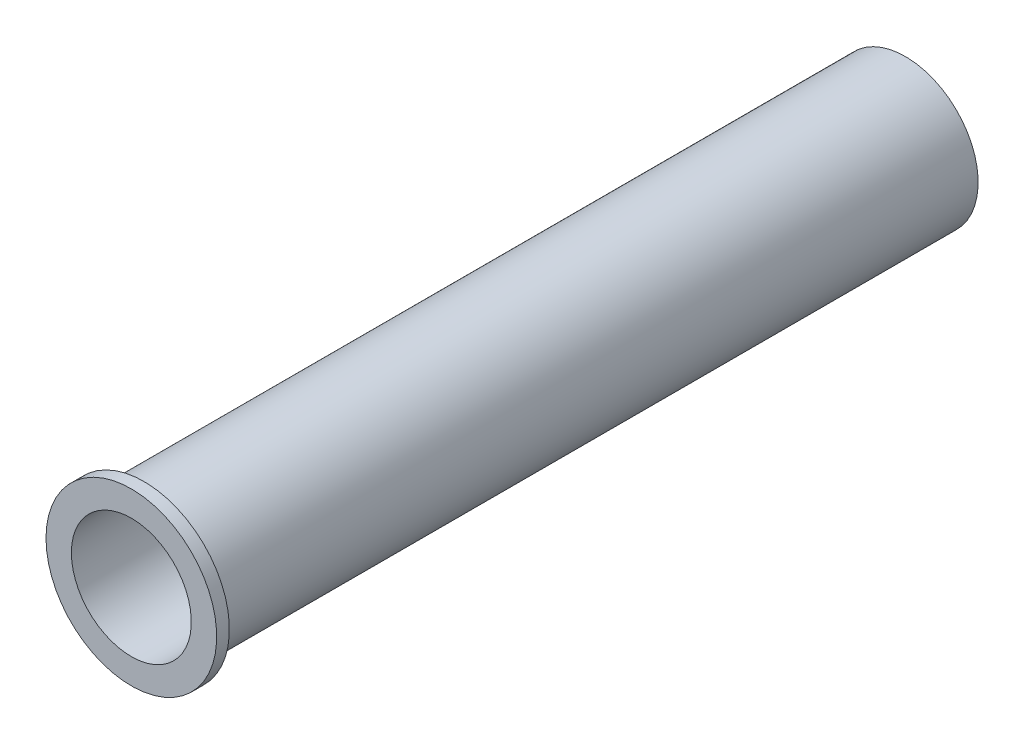
SolidWorks part; units mm, degrees
ref_plane "Alzado" through (0, 0, 0) normal (1, 0, 0) x (0, 1, 0)
ref_plane "Planta" through (0, 0, 0) normal (0, 0, 1) x (0, 1, 0)
ref_plane "Vista lateral" through (0, 0, 0) normal (0, 1, 0) x (-1, 0, 0)
sketch "Croquis1" plane through (0, 0, 0) normal (1, 0, 0) x (0, 1, 0)
  line L0 (9.45, -60) -> (9.45, 60)
  line L1 (9.45, 60) -> (13.45, 60)
  line L2 (13.45, 60) -> (13.45, 58)
  line L3 (13.45, 58) -> (11.45, 58)
  line L4 (11.45, 58) -> (11.45, -62)
  line L5 (11.45, -62) -> (7.95, -62)
  line L6 (7.95, -62) -> (7.95, -60)
  line L7 (7.95, -60) -> (9.45, -60)
  line L8 (0, 0) -> (0, 4.1277) construction
  point P3 (9.45, 0)
  dimension "D1" = 2
  dimension "D2" = 1.5
  dimension "D3" = 2
  dimension "D4" = 2
  dimension "D5" = 2
  dimension "D6" = 26.9
  dimension "D7" = 120
revolve "Revolución1" add sketch "Croquis1" angle 360 about L8
equation "\"D4@Croquis1\"=\"D3@Croquis1\""
equation "\"D5@Croquis1\"=\"D3@Croquis1\""
